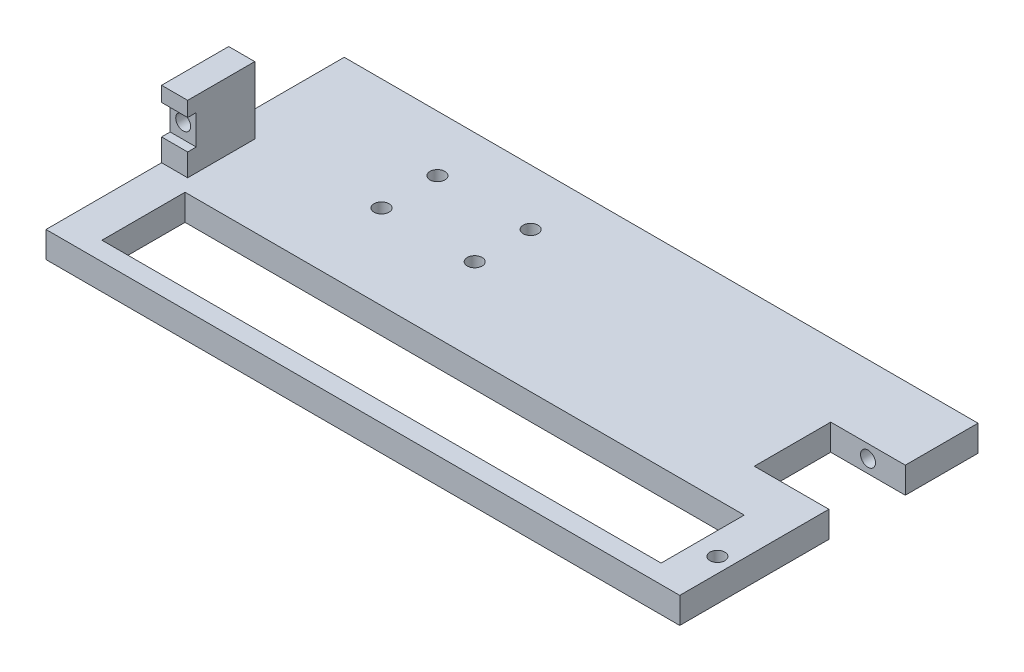
SolidWorks part; units mm, degrees
ref_plane "Front Plane" through (0, 0, 0) normal (0, 0, 1) x (1, 0, 0)
ref_plane "Top Plane" through (0, 0, 0) normal (0, 1, 0) x (1, 0, 0)
ref_plane "Right Plane" through (0, 0, 0) normal (1, 0, 0) x (0, 0, -1)
sketch "Sketch1" plane through (0, 0, 0) normal (0, 1, 0) x (1, 0, 0)
  line L1 (-79.8297, 39.708) -> (90.1703, 39.708)
  line L2 (-79.8297, 39.708) -> (-79.8297, -40.292)
  line L3 (-79.8297, -40.292) -> (90.1703, -40.292)
  line L4 (90.1703, 39.708) -> (90.1703, -40.292)
  dimension "D1" = 170
  dimension "D2" = 80
extrude "Boss-Extrude1" add sketch "Sketch1" along normal blind 7
sketch "Sketch2" plane through (0, 7, 0) normal (0, 1, 0) x (1, 0, 0)
  line L0 (-79.8297, 39.708) -> (-79.8297, -40.292) construction
  line L1 (-79.8297, -40.292) -> (90.1703, -40.292) construction
  line L2 (-79.8297, 8.708) -> (-72.8297, 8.708)
  line L3 (-79.8297, 8.708) -> (-79.8297, -9.292)
  line L4 (-79.8297, -9.292) -> (-72.8297, -9.292)
  line L5 (-72.8297, 8.708) -> (-72.8297, -9.292)
  line L6 (90.1703, 39.708) -> (-79.8297, 39.708) construction
  dimension "D1" = 7
  dimension "D2" = 18
  dimension "D3" = 31
  dimension "D4" = 31
extrude "Boss-Extrude2" add sketch "Sketch2" along normal blind 18
sketch "Sketch3" plane through (0, 0, -8.708) normal (0, 0, -1) x (-1, 0, 0)
  line L0 (79.8297, 25) -> (79.8297, 7) construction
  line L1 (72.8297, 7) -> (79.8297, 7) construction
  circle A0 centre (76.3297, 17) radius 2
  dimension "D1" = 3.5
  dimension "D2" = 10
extrude "Cut-Extrude1" cut sketch "Sketch3" against normal blind 20
sketch "Sketch4" plane through (0, 0, 9.292) normal (0, 0, 1) x (1, 0, 0)
  line L0 (-79.8297, 25) -> (-79.8297, 7) construction
  line L1 (-79.8297, 21) -> (-72.8297, 21)
  line L2 (-79.8297, 21) -> (-79.8297, 13)
  line L3 (-79.8297, 13) -> (-72.8297, 13)
  line L4 (-72.8297, 21) -> (-72.8297, 13)
  line L5 (-72.8297, 25) -> (-72.8297, 7) construction
  line L6 (-79.8297, 7) -> (90.1703, 7) construction
  dimension "D1" = 8
  dimension "D2" = 6
extrude "Cut-Extrude2" cut sketch "Sketch4" against normal blind 2.3
sketch "Sketch5" plane through (0, 7, 0) normal (0, 1, 0) x (1, 0, 0)
  line L0 (-79.8297, -9.292) -> (-79.8297, -40.292) construction
  line L1 (-69.8297, -35.292) -> (80.1703, -35.292)
  line L2 (-69.8297, -35.292) -> (-69.8297, -12.9966)
  line L3 (-69.8297, -12.9966) -> (80.1703, -12.9966)
  line L4 (80.1703, -35.292) -> (80.1703, -12.9966)
  line L5 (90.1703, -40.292) -> (90.1703, 39.708) construction
  line L6 (-79.8297, -40.292) -> (90.1703, -40.292) construction
  dimension "D1" = 10
  dimension "D2" = 10
  dimension "D3" = 5
extrude "Cut-Extrude3" cut sketch "Sketch5" against normal blind 11
sketch "Sketch6" plane through (0, 7, 0) normal (0, 1, 0) x (1, 0, 0)
  line L0 (-79.8297, -40.292) -> (90.1703, -40.292) construction
  line L1 (90.1703, -40.292) -> (90.1703, 39.708) construction
  line L2 (90.1703, 39.708) -> (-79.8297, 39.708) construction
  line L3 (70.1703, -0.292) -> (90.1703, -0.292)
  line L4 (70.1703, -0.292) -> (70.1703, 20.208)
  line L5 (70.1703, 20.208) -> (90.1703, 20.208)
  line L6 (90.1703, -0.292) -> (90.1703, 20.208)
  circle A0 centre (86.1703, -26.192) radius 2
  dimension "D1" = 14.1
  dimension "D2" = 4
  dimension "D3" = 20
  dimension "D4" = 19.5
  dimension "D5" = 20.5
extrude "Cut-Extrude4" cut sketch "Sketch6" against normal blind 11
sketch "Sketch7" plane through (0, 0, -20.208) normal (0, 0, 1) x (1, 0, 0)
  line L0 (90.1703, 0) -> (90.1703, 7) construction
  line L1 (90.1703, 7) -> (70.1703, 7) construction
  circle A0 centre (80.1703, 3.5) radius 2
  dimension "D1" = 10
  dimension "D2" = 3.5
extrude "Cut-Extrude5" cut sketch "Sketch7" against normal blind 25
extrude "Cut-Extrude6" cut sketch "Sketch7<2>" along normal blind 25
sketch "Sketch7<2>" plane through (0, 0, -20.208) normal (0, 0, 1) x (1, 0, 0) same geometry as "Sketch7"
sketch "Sketch10" plane through (0, 0, 0) normal (0, -1, 0) x (1, 0, 0)
  line L0 (-79.8297, -39.708) -> (-79.8297, 40.292) construction
  line L1 (90.1703, -39.708) -> (-79.8297, -39.708) construction
  circle A0 centre (-39.8297, -9.708) radius 2
  circle A1 centre (-39.8297, -24.708) radius 2
  circle A2 centre (-14.8297, -24.708) radius 2
  circle A3 centre (-14.8297, -9.708) radius 2
  dimension "D1" = 40
  dimension "D5" = 25
  dimension "D2" = 40
  dimension "D3" = 15
  dimension "D4" = 15
  dimension "D6" = 25
extrude "Cut-Extrude7" cut sketch "Sketch10" against normal blind 10
